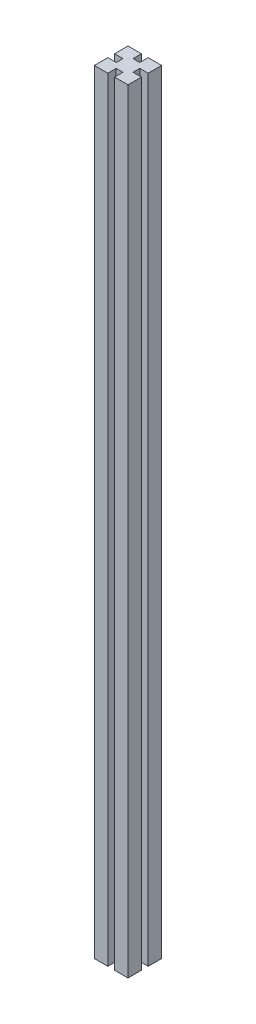
SolidWorks part; units mm, degrees
ref_plane "Front Plane" through (0, 0, 0) normal (0, 0, 1) x (1, 0, 0)
ref_plane "Top Plane" through (0, 0, 0) normal (0, 1, 0) x (1, 0, 0)
ref_plane "Right Plane" through (0, 0, 0) normal (1, 0, 0) x (0, 0, -1)
sketch "Sketch1" plane through (0, 0, 0) normal (0, 1, 0) x (1, 0, 0)
  line L0 (0, 12.5) -> (0, -25) construction
  line L1 (-25, 25) -> (-5, 25)
  line L2 (-25, 25) -> (-25, 5)
  line L3 (-25, -25) -> (-5, -25)
  line L4 (25, 25) -> (25, 5)
  line L5 (-25, 25) -> (25, -25) construction
  line L6 (-25, -25) -> (25, 25) construction
  line L7 (-25, 0) -> (12.5, 0) construction
  line L8 (-5, 25) -> (-5, 12.5)
  line L9 (-5, 12.5) -> (5, 12.5)
  line L10 (-5, -12.5) -> (5, -12.5)
  line L11 (-5, -25) -> (-5, -12.5)
  line L12 (-25, 5) -> (-12.5, 5)
  line L13 (-12.5, 5) -> (-12.5, -5)
  line L14 (12.5, 5) -> (12.5, -5)
  line L15 (25, 5) -> (12.5, 5)
  line L16 (25, -5) -> (12.5, -5)
  line L17 (-25, -5) -> (-12.5, -5)
  line L18 (5, -25) -> (5, -12.5)
  line L19 (5, 25) -> (5, 12.5)
  line L20 (5, 25) -> (25, 25)
  line L21 (25, -5) -> (25, -25)
  line L22 (5, -25) -> (25, -25)
  line L23 (-25, -5) -> (-25, -25)
  point P0 (0, 0)
  point P24 (12.5, 0)
  point P25 (-12.5, 0)
  point P28 (0, -12.5)
  point P29 (0, 12.5)
  dimension "D1" = 50
  dimension "D2" = 10
  dimension "D3" = 12.5
  dimension "D4" = 50
extrude "Boss-Extrude1" add sketch "Sketch1" along normal blind 1150
extrude "Boss-Extrude2" add sketch "Sketch1<2>" along normal blind 10
sketch "Sketch1<2>" plane through (0, 0, 0) normal (0, 1, 0) x (1, 0, 0) same geometry as "Sketch1"
